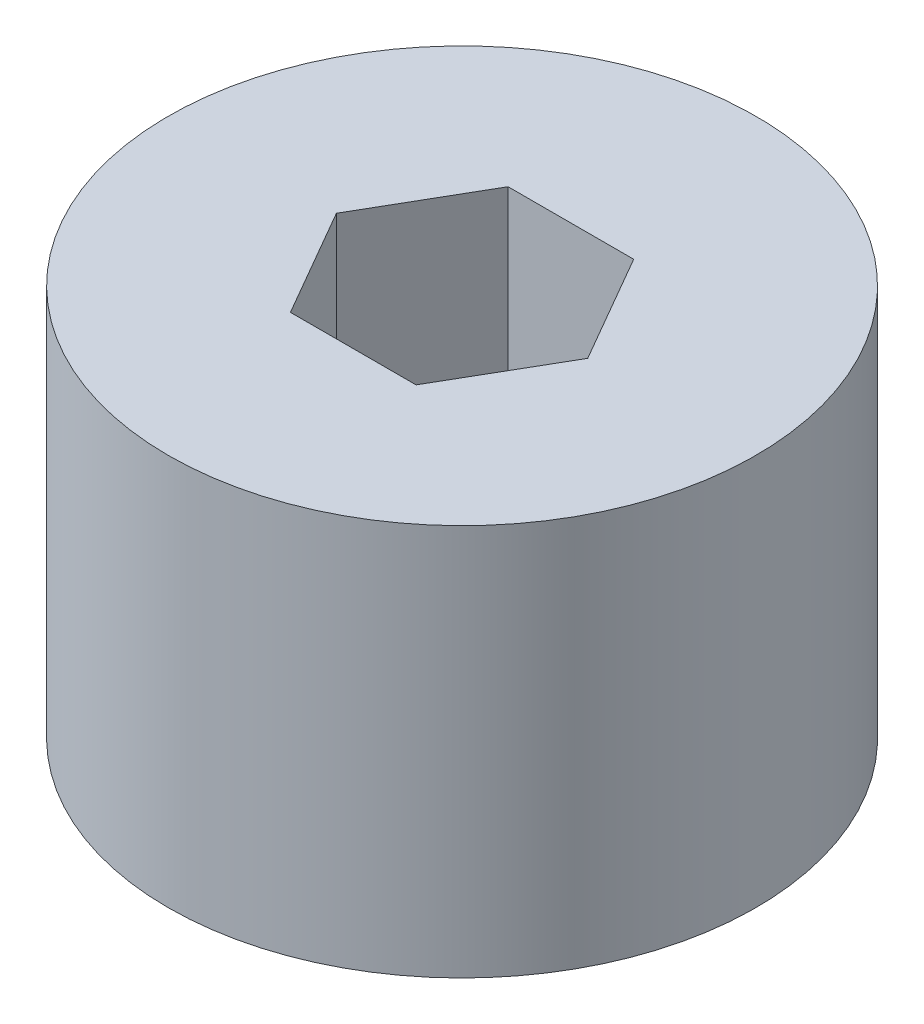
SolidWorks part; units mm, degrees
ref_plane "Front" through (0, 0, 0) normal (0, 0, 1) x (1, 0, 0)
ref_plane "Top" through (0, 0, 0) normal (0, 1, 0) x (1, 0, 0)
ref_plane "Right" through (0, 0, 0) normal (1, 0, 0) x (0, 0, -1)
sketch "Sketch1" plane through (0, 0, 0) normal (0, 1, 0) x (1, 0, 0)
  line L1 (7.3323, 0) -> (3.6662, 6.35)
  line L2 (3.6662, 6.35) -> (-3.6662, 6.35)
  line L3 (-3.6662, 6.35) -> (-7.3323, 0)
  line L4 (-7.3323, 0) -> (-3.6662, -6.35)
  line L5 (-3.6662, -6.35) -> (3.6662, -6.35)
  line L6 (3.6662, -6.35) -> (7.3323, 0)
  circle A0 centre (0, 0) radius 17.145
  circle A1 centre (0, 0) radius 6.35 construction
  dimension "D1" = 34.29
  dimension "D2" = 12.7
extrude "Boss-Extrude1" add sketch "Sketch1" along normal blind 22.86
extrude "Boss-Extrude2" add sketch "Sketch1<2>" along normal blind 6.35 contours L5 L6 L1 L2 L3 L4 region at (0, 0, 0)
sketch "Sketch1<2>" plane through (0, 0, 0) normal (0, 1, 0) x (1, 0, 0) same geometry as "Sketch1"
